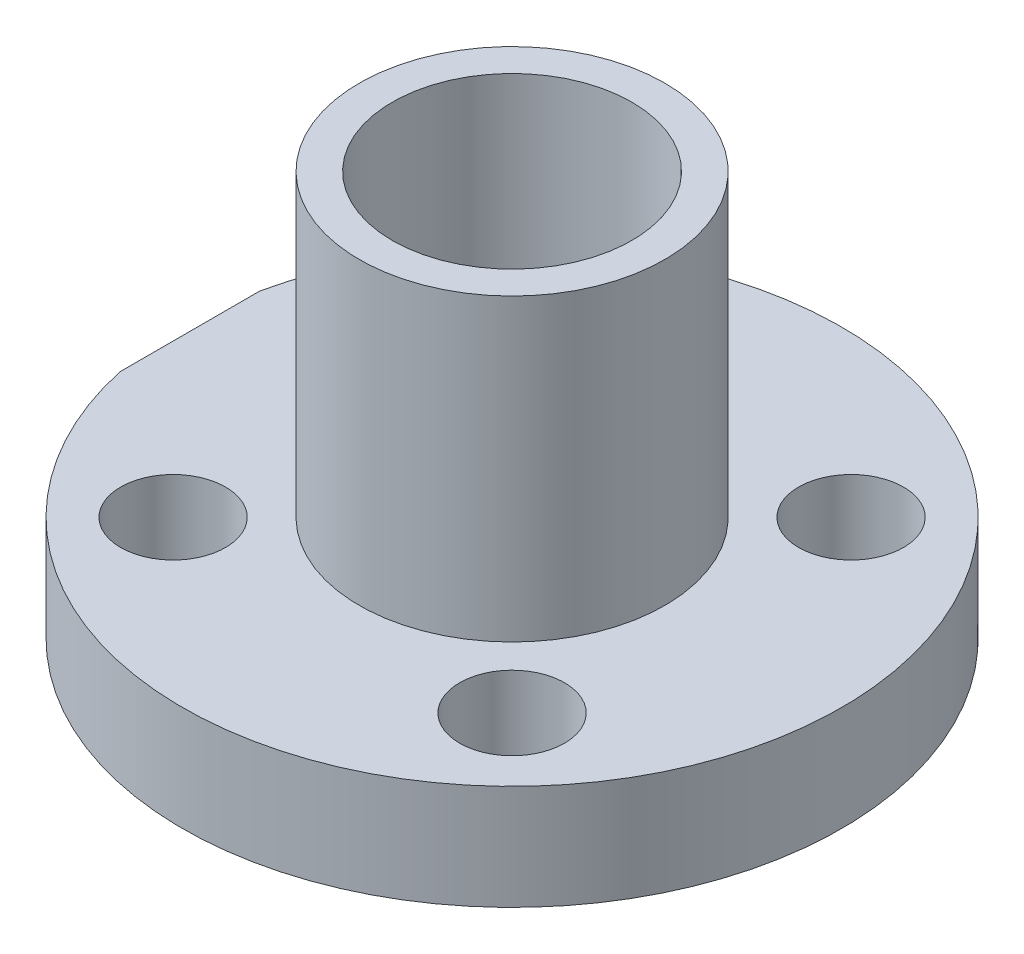
SolidWorks part; units mm, degrees
material "Messing"
ref_plane "Ebene vorne" through (0, 0, 0) normal (0, 0, 1) x (1, 0, 0)
ref_plane "Ebene oben" through (0, 0, 0) normal (0, 1, 0) x (1, 0, 0)
ref_plane "Ebene rechts" through (0, 0, 0) normal (1, 0, 0) x (0, 0, -1)
sketch "Skizze1" plane through (0, 0, 0) normal (0, 0, 1) x (1, 0, 0)
  line L0 (0, 0) -> (0, 10.6853) construction
  line L1 (-4, 0) -> (-4, 13.5)
  line L2 (-4, 13.5) -> (-5.1, 13.5)
  line L3 (-5.1, 13.5) -> (-5.1, 3.5)
  line L4 (-5.1, 3.5) -> (-11, 3.5)
  line L5 (-11, 3.5) -> (-11, 0)
  line L6 (-11, 0) -> (-5.1, 0)
  line L7 (-5.1, 0) -> (-5.1, -1.5)
  line L8 (-5.1, -1.5) -> (-4, -1.5)
  line L9 (-4, -1.5) -> (-4, 0)
  dimension "D1" = 10
  dimension "D2" = 3.5
  dimension "D3" = 1.5
  dimension "D4" = 5.1
  dimension "D5" = 8
  dimension "D6" = 11
revolve "Rotation1" add sketch "Skizze1" angle 360 about L0
hole_wizard "Ø3.5 (3.5) Durchmesser Bohrung1" positions "Skizze3" profile "Skizze4" hole size "Ø3.5" standard "DIN" end condition through all
sketch "Skizze3" plane through (0, 3.5, 0) normal (0, 1, 0) x (1, 0, 0)
  line L8 (-5.6569, 5.6569) -> (5.6569, 5.6569) construction
  line L9 (-5.6569, 5.6569) -> (-5.6569, -5.6569) construction
  line L10 (-5.6569, -5.6569) -> (5.6569, -5.6569) construction
  line L11 (5.6569, 5.6569) -> (5.6569, -5.6569) construction
  circle A0 centre (0, 0) radius 8 construction
  point P80 (-5.6569, 5.6569)
  point P81 (5.6569, -5.6569)
  point P84 (-5.6569, -5.6569)
  point P85 (5.6569, 5.6569)
  dimension "D1" = 16
sketch "Skizze4" plane through (5.6569, 3.5, -5.6569) normal (1, 0, 0) x (0, 0, 1)
  line L0 (0, 0) -> (0, 5)
  line L1 (0, 5) -> (1.75, 5)
  line L2 (1.75, 5) -> (1.75, 0)
  line L5 (1.75, 0) -> (0, 0)
  line L11 (0, -6.35) -> (0, 107.95) construction
  dimension "Bohrerdurchmesser" = 3.5
  dimension "Bohrungstiefe" = 5
sketch "Skizze5" plane through (0, 3.5, 0) normal (0, 1, 0) x (1, 0, 0)
  line L0 (-11, 0) -> (0, 0) construction
  line L1 (-11.25, -25) -> (-10.75, -25)
  line L2 (-11.25, -25) -> (-11.25, 25)
  line L3 (-11.25, 25) -> (-10.75, 25)
  line L4 (-10.75, -25) -> (-10.75, 25)
  line L5 (-11.25, -25) -> (-10.75, 25) construction
  line L6 (-11.25, 25) -> (-10.75, -25) construction
  circle A0 centre (0, 0) radius 11 construction
  point P0 (-11, 0)
  dimension "D1" = 50
  dimension "D2" = 0.5
extrude "Schnitt-Linear austragen1" cut sketch "Skizze5" against normal through all
